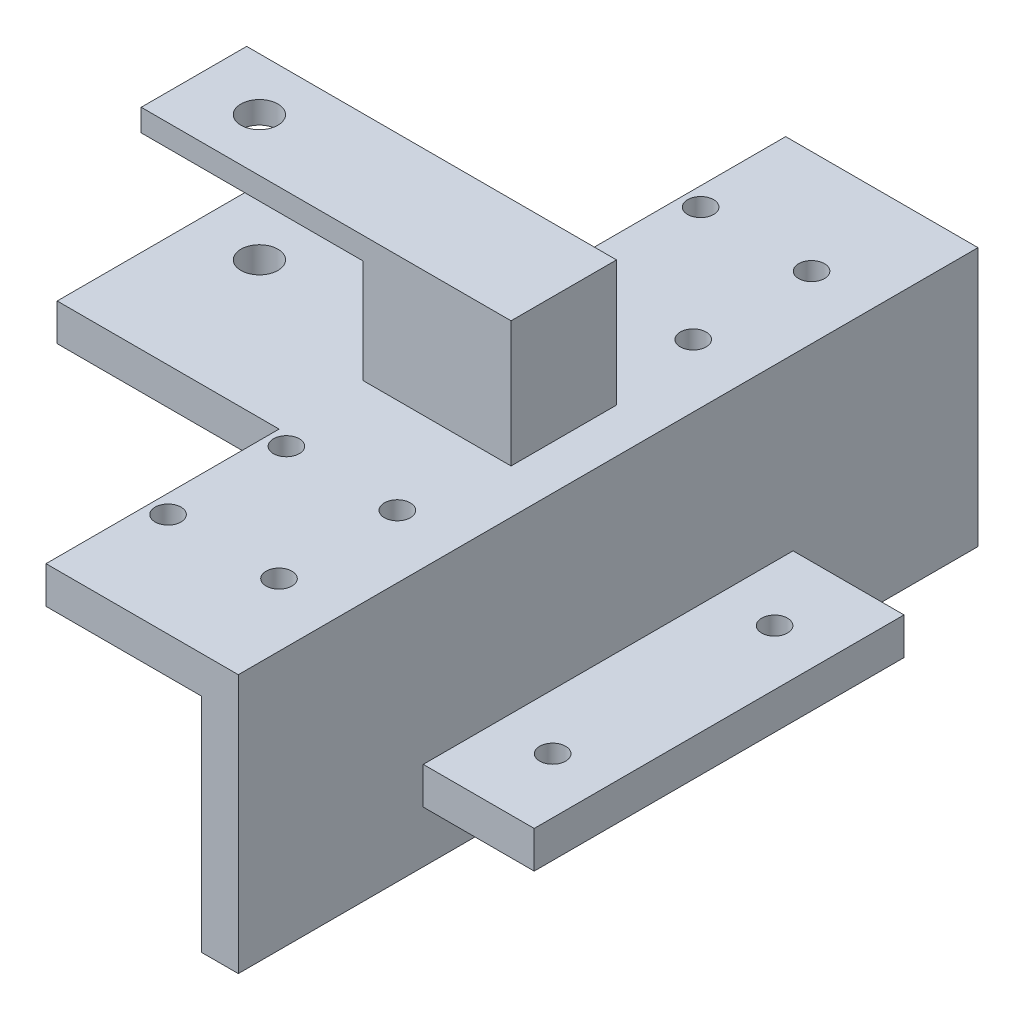
SolidWorks part; units mm, degrees
ref_plane "Front Plane" through (0, 0, 0) normal (0, 0, 1) x (1, 0, 0)
ref_plane "Top Plane" through (0, 0, 0) normal (0, 1, 0) x (1, 0, 0)
ref_plane "Right Plane" through (0, 0, 0) normal (1, 0, 0) x (0, 0, -1)
sketch "Sketch1" plane through (0, 0, 0) normal (0, 1, 0) x (1, 0, 0)
  line L0 (0, 50) -> (0, -50) construction
  line L1 (-10, 50) -> (10, 50)
  line L2 (-10, 50) -> (-10, -50)
  line L3 (-10, -50) -> (10, -50)
  line L4 (10, 50) -> (10, -50) construction
  line L5 (-10, 50) -> (10, -50) construction
  line L6 (-10, -50) -> (10, 50) construction
  line L7 (-7.5, 36) -> (7.5, 36) construction
  line L8 (-7.5, 36) -> (7.5, 20) construction
  line L9 (-10, 0) -> (10, 0) construction
  line L10 (-7.5, -36) -> (7.5, -20) construction
  line L11 (-7.5, -36) -> (7.5, -36) construction
  line L12 (-7.5, 20) -> (7.5, 20) construction
  line L13 (10, 50) -> (11, 50)
  line L14 (11, 50) -> (11, -50)
  line L15 (11, -50) -> (10, -50)
  circle A0 centre (-7.5, 36) radius 1.75
  circle A1 centre (7.5, 36) radius 1.75
  circle A2 centre (-7.5, 20) radius 1.75
  circle A3 centre (7.5, 20) radius 1.75
  circle A4 centre (7.5, -20) radius 1.75
  circle A5 centre (-7.5, -20) radius 1.75
  circle A6 centre (7.5, -36) radius 1.75
  circle A7 centre (-7.5, -36) radius 1.75
  point P0 (0, 0)
  point P16 (0, 36)
  dimension "D2" = 3.5
  dimension "D1" = 20
  dimension "D3" = 15
  dimension "D4" = 16
  dimension "D5" = 100
  dimension "D6" = 20
  dimension "D7" = 1
extrude "Boss-Extrude1" add sketch "Sketch1" along normal blind 5
sketch "Sketch2" plane through (11, 0, 0) normal (1, 0, 0) x (0, 0, -1)
  line L1 (-50, 5) -> (50, 5)
  line L2 (-50, 5) -> (-50, -30)
  line L3 (-50, -30) -> (50, -30)
  line L5 (50, 5) -> (50, -30)
  line L6 (50, 5) -> (50, 0) construction
  line L7 (-50, 5) -> (-50, 0) construction
  line L8 (-50, 5) -> (50, 5) construction
  dimension "D1" = 35
extrude "Boss-Extrude2" add sketch "Sketch2" along normal blind 5
sketch "Sketch3" plane through (16, 0, 0) normal (1, 0, 0) x (0, 0, -1)
  line L0 (0, 5) -> (0, -30) construction
  line L1 (-25, -18) -> (25, -18)
  line L2 (-25, -18) -> (-25, -23)
  line L3 (-25, -23) -> (25, -23)
  line L4 (25, -18) -> (25, -23)
  line L5 (50, 5) -> (-50, 5) construction
  line L6 (-50, -30) -> (50, -30) construction
  point P10 (0, -18)
  dimension "D1" = 5
  dimension "D2" = 50
  dimension "D3" = 7
extrude "Boss-Extrude3" add sketch "Sketch3" along normal blind 15
sketch "Sketch4" plane through (0, -18, 0) normal (0, 1, 0) x (1, 0, 0)
  line L0 (16, 0) -> (31, 0) construction
  line L1 (16, 25) -> (16, -25) construction
  line L2 (31, 25) -> (31, -25) construction
  line L3 (23.5, -15) -> (23.5, 15) construction
  circle A0 centre (23.5, 15) radius 1.75
  circle A1 centre (23.5, -15) radius 1.75
  point P8 (23.5, 0)
  dimension "D1" = 30
  dimension "D2" = 3.5
extrude "Cut-Extrude1" cut sketch "Sketch4" against normal through all
sketch "Sketch5" plane through (0, 5, 0) normal (0, 1, 0) x (1, 0, 0)
  line L5 (-10, 50) -> (-10, -50) construction
  line L6 (-10, 7.129) -> (10, 7.129)
  line L7 (-10, 7.129) -> (-10, -7.129)
  line L8 (-10, -7.129) -> (10, -7.129)
  line L9 (10, 7.129) -> (10, -7.129)
  line L10 (10, 0) -> (-10, 0) construction
extrude "Boss-Extrude4" add sketch "Sketch5" along normal blind 17
sketch "Sketch6" plane through (-10, 0, 0) normal (-1, 0, 0) x (0, 0, 1)
  line L10 (7.129, 22) -> (7.129, 5) construction
  line L11 (-7.129, 22) -> (7.129, 22)
  line L12 (-7.129, 22) -> (-7.129, 19)
  line L13 (-7.129, 19) -> (7.129, 19)
  line L14 (7.129, 22) -> (7.129, 19)
  line L15 (-50, 5) -> (-7.129, 5) construction
  line L16 (-18.4885, 5) -> (18.4885, 5)
  line L17 (-18.4885, 5) -> (-18.4885, 0)
  line L18 (-18.4885, 0) -> (18.4885, 0)
  line L19 (18.4885, 5) -> (18.4885, 0)
  line L20 (-50, 0) -> (50, 0) construction
  dimension "D1" = 14
extrude "Boss-Extrude5" add sketch "Sketch6" along normal blind 30
sketch "Sketch7" plane through (0, 5, 0) normal (0, 1, 0) x (1, 0, 0)
  line L0 (-10, 50) -> (-10, 18.4885) construction
  circle A0 centre (-31.15, 0) radius 2.5
  dimension "D1" = 5
  dimension "D2" = 21.15
extrude "Cut-Extrude2" cut sketch "Sketch7" along normal through all both and the other way through all
